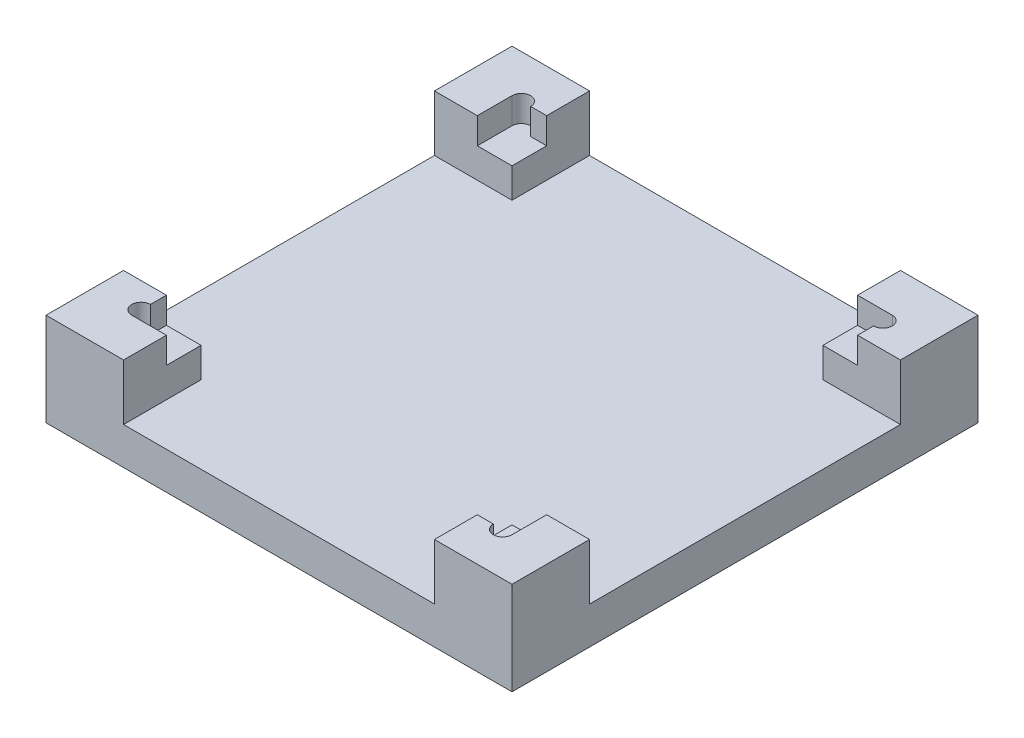
SolidWorks part; units mm, degrees
ref_plane "Front Plane" through (0, 0, 0) normal (0, 0, 1) x (1, 0, 0)
ref_plane "Top Plane" through (0, 0, 0) normal (0, 1, 0) x (1, 0, 0)
ref_plane "Right Plane" through (0, 0, 0) normal (1, 0, 0) x (0, 0, -1)
sketch "Sketch1" plane through (0, 0, 0) normal (0, 1, 0) x (1, 0, 0)
  line L1 (0, 0) -> (125, 0)
  line L2 (0, 0) -> (0, 125)
  line L3 (0, 125) -> (125, 125)
  line L4 (125, 0) -> (125, 125)
  dimension "D1" = 125
  dimension "D2" = 125
extrude "Boss-Extrude1" add sketch "Sketch1" along normal blind 25
sketch "Sketch2" plane through (0, 25, 0) normal (0, 1, 0) x (1, 0, 0)
  line L0 (0, 62.5) -> (125, 62.5) construction
  line L1 (11.5, 11.5) -> (113.5, 11.5)
  line L2 (11.5, 11.5) -> (11.5, 113.5)
  line L3 (11.5, 113.5) -> (113.5, 113.5)
  line L4 (113.5, 11.5) -> (113.5, 113.5)
  line L5 (0, 125) -> (0, 0) construction
  line L6 (62.5, 0) -> (62.5, 125) construction
  line L7 (0, 0) -> (125, 0) construction
  line L8 (125, 0) -> (125, 125) construction
  line L9 (125, 125) -> (0, 125) construction
  point P10 (11.5, 62.5)
  point P17 (62.5, 11.5)
  dimension "D1" = 102
  dimension "D2" = 102
extrude "Cut-Extrude1" cut sketch "Sketch2" against normal blind 15
sketch "Sketch4" plane through (0, 25, 0) normal (0, 1, 0) x (1, 0, 0)
  line L0 (125, 125) -> (0, 125) construction
  line L1 (104.2, 125) -> (20.8, 125)
  line L2 (104.2, 125) -> (104.2, 113.5)
  line L3 (104.2, 113.5) -> (20.8, 113.5)
  line L4 (20.8, 125) -> (20.8, 113.5)
  line L5 (113.5, 113.5) -> (11.5, 113.5) construction
  line L6 (11.5, 113.5) -> (11.5, 11.5) construction
  line L7 (11.5, 104.2) -> (0, 104.2)
  line L8 (11.5, 104.2) -> (11.5, 20.8)
  line L9 (11.5, 20.8) -> (0, 20.8)
  line L10 (0, 104.2) -> (0, 20.8)
  line L11 (0, 125) -> (0, 0) construction
  line L12 (11.5, 11.5) -> (113.5, 11.5) construction
  line L13 (104.2, 11.5) -> (20.8, 11.5)
  line L14 (104.2, 11.5) -> (104.2, 0)
  line L15 (104.2, 0) -> (20.8, 0)
  line L16 (20.8, 11.5) -> (20.8, 0)
  line L17 (0, 0) -> (125, 0) construction
  line L18 (125, 0) -> (125, 125) construction
  line L19 (125, 104.2) -> (113.5, 104.2)
  line L20 (125, 104.2) -> (125, 20.8)
  line L21 (125, 20.8) -> (113.5, 20.8)
  line L22 (113.5, 104.2) -> (113.5, 20.8)
  line L23 (113.5, 11.5) -> (113.5, 113.5) construction
  point P32 (5.75, 20.8)
  dimension "D1" = 9.3
  dimension "D2" = 9.3
  dimension "D3" = 9.3
  dimension "D4" = 9.3
  dimension "D5" = 9.3
  dimension "D6" = 9.3
  dimension "D7" = 9.3
  dimension "D8" = 9.3
extrude "Cut-Extrude2" cut sketch "Sketch4" against normal blind 15
sketch "Sketch5" plane through (0, 10, 0) normal (0, 1, 0) x (1, 0, 0)
  line L1 (113.5, 11.5) -> (104.2, 11.5)
  line L2 (113.5, 11.5) -> (113.5, 20.8)
  line L3 (113.5, 20.8) -> (104.2, 20.8)
  line L4 (104.2, 11.5) -> (104.2, 20.8)
  line L5 (11.5, 11.5) -> (20.8, 11.5)
  line L6 (11.5, 11.5) -> (11.5, 20.8)
  line L7 (11.5, 20.8) -> (20.8, 20.8)
  line L8 (20.8, 11.5) -> (20.8, 20.8)
  line L9 (11.5, 113.5) -> (20.8, 113.5)
  line L10 (11.5, 113.5) -> (11.5, 104.2)
  line L11 (11.5, 104.2) -> (20.8, 104.2)
  line L12 (20.8, 113.5) -> (20.8, 104.2)
  line L13 (113.5, 113.5) -> (104.2, 113.5)
  line L14 (113.5, 113.5) -> (113.5, 104.2)
  line L15 (113.5, 104.2) -> (104.2, 104.2)
  line L16 (104.2, 113.5) -> (104.2, 104.2)
  dimension "D1" = 9.3
  dimension "D2" = 9.3
  dimension "D3" = 9.3
  dimension "D4" = 9.3
  dimension "D5" = 9.3
  dimension "D6" = 9.3
  dimension "D7" = 9.3
  dimension "D8" = 9.3
extrude "Boss-Extrude2" add sketch "Sketch5" along normal blind 8
sketch "Sketch6" plane through (0, 25, 0) normal (0, 1, 0) x (1, 0, 0)
  line L0 (11.5, 20.8) -> (11.5, 11.5) construction
  line L1 (11.5, 11.5) -> (11.5, 16.5)
  line L2 (104.2, 11.5) -> (113.5, 11.5) construction
  line L3 (113.5, 11.5) -> (108.5, 11.5)
  line L4 (113.5, 104.2) -> (113.5, 113.5) construction
  line L5 (113.5, 108.5) -> (113.5, 113.5)
  line L6 (20.8, 113.5) -> (11.5, 113.5) construction
  line L7 (11.5, 113.5) -> (16.5, 113.5)
  arc A0 (11.5, 11.5) -> (11.5, 16.5) centre (11.5, 14) cw
  arc A1 (113.5, 11.5) -> (108.5, 11.5) centre (111, 11.5) cw
  arc A2 (113.5, 113.5) -> (113.5, 108.5) centre (113.5, 111) cw
  arc A3 (11.5, 113.5) -> (16.5, 113.5) centre (14, 113.5) cw
  dimension "D1" = 2.5
  dimension "D2" = 2.5
  dimension "D3" = 2.5
  dimension "D4" = 2.5
extrude "Cut-Extrude3" cut sketch "Sketch6" against normal up to surface (7 mm away) up to face at (108.85, 18, -16.15)
